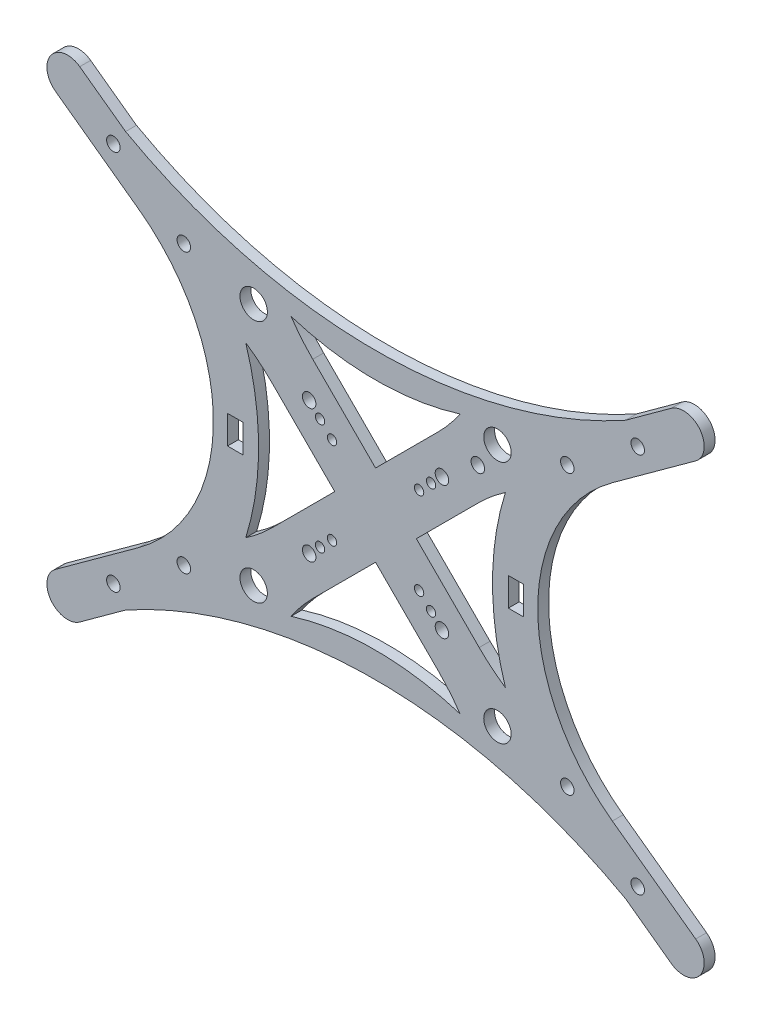
SolidWorks part; units mm, degrees
material "PPS"
ref_plane "前视基准面" through (0, 0, 0) normal (0, 0, 1) x (1, 0, 0)
ref_plane "上视基准面" through (0, 0, 0) normal (0, 1, 0) x (1, 0, 0)
ref_plane "右视基准面" through (0, 0, 0) normal (1, 0, 0) x (0, 0, -1)
sketch "草图7" plane through (0, 0, 0) normal (0, 0, 1) x (1, 0, 0)
  line L0 (-137.4469, 0) -> (193.7386, 0) construction
  line L1 (0, 90.5001) -> (0, -188.7446) construction
  line L2 (0, 0) -> (86.3378, -62.728) construction
  line L61 (-67.9485, -55.2388) -> (-57.4206, -47.5898)
  line L62 (-73.5325, -47.5531) -> (-54.395, -33.649)
  line L66 (-67.9485, 55.2388) -> (-57.4206, 47.5898)
  line L82 (-73.5325, 47.5531) -> (-54.395, 33.649)
  line L93 (73.5325, 47.5531) -> (54.395, 33.649)
  line L94 (-34, -3.25) -> (-34, 3.25) construction
  line L95 (67.9485, 55.2388) -> (57.4206, 47.5898)
  line L104 (15.25, 15.25) -> (0, 0) construction
  line L105 (67.9485, -55.2388) -> (57.4206, -47.5898)
  line L106 (73.5325, -47.5531) -> (54.395, -33.649)
  line L107 (0, 0) -> (86.3378, 62.728) construction
  circle A40 centre (10, 10) radius 1.075
  circle A65 centre (12.75, 12.75) radius 1.075
  circle A66 centre (15.25, 15.25) radius 1.55
  circle A73 centre (15.25, -15.25) radius 1.55
  circle A74 centre (12.75, -12.75) radius 1.075
  circle A75 centre (10, -10) radius 1.075
  circle A76 centre (28, -28) radius 3.15
  circle A89 centre (28, 28) radius 3.15
  arc A132 (67.9485, 55.2388) -> (73.5325, 47.5531) centre (70.7405, 51.396) cw
  arc A133 (54.395, 33.649) -> (54.395, -33.649) centre (78.8424, 0) ccw
  circle A134 centre (60.2246, 43.7557) radius 1.55
  arc A135 (-57.4206, -47.5898) -> (57.4206, -47.5898) centre (0, -151.3241) cw
  circle A136 centre (-60.2246, 43.7557) radius 1.55
  arc A138 (-54.395, 33.649) -> (-54.395, -33.649) centre (-78.8424, 0) cw
  arc A139 (-67.9485, 55.2388) -> (-73.5325, 47.5531) centre (-70.7405, 51.396) ccw
  circle A152 centre (-28, 28) radius 3.15
  circle A153 centre (-28, -28) radius 3.15
  circle A154 centre (-10, -10) radius 1.075
  circle A155 centre (-12.75, -12.75) radius 1.075
  circle A156 centre (-15.25, -15.25) radius 1.55
  circle A157 centre (-15.25, 15.25) radius 1.55
  circle A158 centre (-12.75, 12.75) radius 1.075
  circle A159 centre (-10, 10) radius 1.075
  arc A166 (-57.4206, 47.5898) -> (57.4206, 47.5898) centre (0, 151.3241) ccw
  arc A167 (67.9485, -55.2388) -> (73.5325, -47.5531) centre (70.7405, -51.396) ccw
  arc A172 (-67.9485, -55.2388) -> (-73.5325, -47.5531) centre (-70.7405, -51.396) cw
  circle A176 centre (60.2246, -43.7557) radius 1.55
  circle A177 centre (44.0442, -32) radius 1.55
  circle A178 centre (44.0442, 32) radius 1.55
  circle A179 centre (-44.0442, 32) radius 1.55
  circle A180 centre (-60.2246, -43.7557) radius 1.55
  circle A181 centre (-44.0442, -32) radius 1.55
  point P49 (-37.25, 0)
  dimension "D2" = 2.75
  dimension "D4" = 2.5
  dimension "D1" = 2.15
  dimension "D3" = 3.1
  dimension "D6" = 3.1
  dimension "D10" = 10
  dimension "D5" = 45
  dimension "D7" = 4.75
  dimension "D8" = 3.25
  dimension "D9" = 10
  dimension "D11" = 12.75
  dimension "D16" = 36
sketch "草图8" plane through (0, 0, 0) normal (0, 0, 1) x (1, 0, 0)
  line L0 (-96.7808, 0) -> (86.8563, 0) construction
  line L1 (0, 52.226) -> (0, -62.4511) construction
  line L2 (34, -3.25) -> (30.5, -3.25)
  line L3 (-34, 3.25) -> (-30.5, 3.25)
  line L4 (-34, 3.25) -> (-34, -3.25)
  line L5 (-34, -3.25) -> (-30.5, -3.25)
  line L6 (-30.5, 3.25) -> (-30.5, -3.25)
  line L7 (30.5, 3.25) -> (30.5, -3.25)
  line L8 (34, 3.25) -> (30.5, 3.25)
  line L9 (34, 3.25) -> (34, -3.25)
  dimension "D1" = 30.5
  dimension "D2" = 6.5
  dimension "D3" = 3.5
sketch "草图6" plane through (0, 0, 0) normal (0, 0, 1) x (1, 0, 0)
  line L3 (-23.8014, 14.4296) -> (-9.3719, 0)
  line L9 (-58.8867, 0) -> (57.6096, 0) construction
  line L14 (-23.8014, -14.4296) -> (-9.3719, 0)
  line L15 (0, 29.8455) -> (0, -115.5328) construction
  line L29 (14.4296, 23.8014) -> (0, 9.3719)
  line L30 (-14.4296, 23.8014) -> (0, 9.3719)
  line L31 (23.8014, -14.4296) -> (9.3719, 0)
  line L32 (23.8014, 14.4296) -> (9.3719, 0)
  line L33 (-14.4296, -23.8014) -> (0, -9.3719)
  line L34 (14.4296, -23.8014) -> (0, -9.3719)
  arc A18 (-23.8014, 14.4296) -> (-29.8202, 19.4008) centre (-52.8883, -14.6573) ccw
  arc A19 (-23.8014, -14.4296) -> (-29.8202, -19.4008) centre (-52.8883, 14.6573) cw
  arc A20 (-29.8202, -19.4008) -> (-29.8202, 19.4008) centre (-91.9966, 0) ccw
  arc A33 (-14.4296, 23.8014) -> (-19.4008, 29.8202) centre (14.6573, 52.8883) cw
  arc A34 (-19.4008, 29.8202) -> (19.4008, 29.8202) centre (0, 91.9966) ccw
  arc A35 (14.4296, 23.8014) -> (19.4008, 29.8202) centre (-14.6573, 52.8883) ccw
  arc A36 (23.8014, 14.4296) -> (29.8202, 19.4008) centre (52.8883, -14.6573) cw
  arc A37 (29.8202, 19.4008) -> (29.8202, -19.4008) centre (91.9966, 0) ccw
  arc A38 (23.8014, -14.4296) -> (29.8202, -19.4008) centre (52.8883, 14.6573) ccw
  arc A39 (14.4296, -23.8014) -> (19.4008, -29.8202) centre (-14.6573, -52.8883) cw
  arc A40 (19.4008, -29.8202) -> (-19.4008, -29.8202) centre (0, -91.9966) ccw
  arc A41 (-14.4296, -23.8014) -> (-19.4008, -29.8202) centre (14.6573, -52.8883) ccw
  point P49 (0, 0)
  dimension "D1" = 4
extrude "主结构-厚度还是得2.5, 不然铝柱不好选" add sketch "草图7" along normal blind 2.5
extrude "切除-拉伸2" cut sketch "草图6" along normal through all
extrude "切除-拉伸3" cut sketch "草图8" along normal through all
sketch "计算机板和PCB结构" plane through (0, 0, 0) normal (0, 0, 1) x (1, 0, 0)
  line L5 (0, 0) -> (0, 133.3353) construction
  line L6 (0, 0) -> (133.1914, 0) construction
  circle A1 centre (23.5, 21.7128) radius 1.55
  circle A9 centre (23.5, 21.7128) radius 1.55 construction
  circle A10 centre (-32, 42) radius 1.55
  circle A11 centre (32, 42) radius 1.55
  circle A12 centre (32, 42) radius 1.55 construction
  circle A13 centre (-32, 42) radius 1.55 construction
  circle A14 centre (-36, -43) radius 1.55
  circle A15 centre (36, -43) radius 1.55
  circle A16 centre (-29.25, -40.5) radius 1.55
  circle A17 centre (29.25, -40.5) radius 1.55
  circle A18 centre (-17.5, 47.5) radius 1.55
  circle A19 centre (17.5, 47.5) radius 1.55
  point P27 (0, 0)
extrude "计算机板孔位和PCB孔位" cut sketch "计算机板和PCB结构" along normal through all contours A10 | A18 | A19 | A11 | A1 | A14 | A16 | A17 | A15 region at (23.5, 21.7128, 0) region at (-32, 42, 0) region at (32, 42, 0) region at (-36, -43, 0) region at (36, -43, 0) region at (-29.25, -40.5, 0) region at (29.25, -40.5, 0) region at (-17.5, 47.5, 0) region at (17.5, 47.5, 0)
